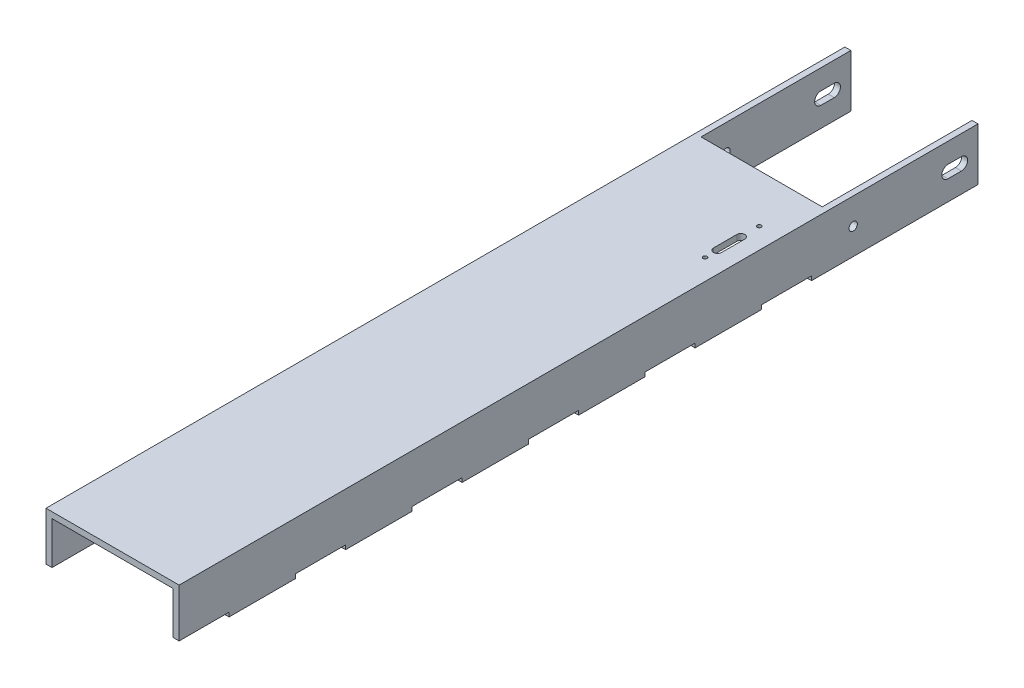
SolidWorks part; units mm, degrees
ref_plane "Front Plane" through (0, 0, 0) normal (0, 0, 1) x (1, 0, 0)
ref_plane "Top Plane" through (0, 0, 0) normal (0, 1, 0) x (1, 0, 0)
ref_plane "Right Plane" through (0, 0, 0) normal (1, 0, 0) x (0, 0, -1)
sketch "Sketch1" plane through (0, 0, 0) normal (0, 0, 1) x (1, 0, 0)
  line L0 (-50.8, 0) -> (50.8, 0)
  line L1 (50.8, 0) -> (50.8, -40.132)
  line L2 (50.8, -40.132) -> (46.228, -40.132)
  line L3 (46.228, -40.132) -> (46.228, -4.572)
  line L4 (46.228, -4.572) -> (-46.228, -4.572)
  line L5 (-46.228, -4.572) -> (-46.228, -40.132)
  line L6 (-46.228, -40.132) -> (-50.8, -40.132)
  line L7 (-50.8, -40.132) -> (-50.8, 0)
  point P8 (0, 0)
  dimension "D1" = 40.132
  dimension "D2" = 4.572
  dimension "D3" = 4.572
  dimension "D4" = 101.6
extrude "Boss-Extrude1" add sketch "Sketch1" along normal blind 609.6
sketch "Sketch3" plane through (0, 0, 0) normal (0, 1, 0) x (1, 0, 0)
  line L0 (50.8, 0) -> (-50.8, 0) construction
  line L1 (-46.228, -114.3) -> (46.228, -114.3)
  line L2 (-46.228, -114.3) -> (-46.228, 0)
  line L3 (-46.228, 0) -> (46.228, 0)
  line L4 (46.228, -114.3) -> (46.228, 0)
  line L5 (-46.228, -114.3) -> (46.228, 0) construction
  line L6 (-46.228, 0) -> (46.228, -114.3) construction
  line L7 (-46.228, -609.6) -> (-46.228, 0) construction
  line L8 (46.228, -609.6) -> (46.228, 0) construction
  line L9 (34.925, -165.1) -> (34.925, -182.88) construction
  line L10 (37.973, -165.1) -> (37.973, -182.88)
  line L11 (31.877, -165.1) -> (31.877, -182.88)
  arc A0 (37.973, -165.1) -> (31.877, -165.1) centre (34.925, -165.1) ccw
  arc A1 (31.877, -182.88) -> (37.973, -182.88) centre (34.925, -182.88) ccw
  circle A2 centre (34.925, -151.13) radius 1.524
  circle A3 centre (34.925, -192.405) radius 1.524
  point P0 (0, -57.15)
  point P13 (34.925, -173.99)
  dimension "D2" = 6.096
  dimension "D6" = 3.048
  dimension "D1" = 114.3
  dimension "D3" = 17.78
  dimension "D4" = 50.8
  dimension "D5" = 8.255
  dimension "D7" = 13.97
  dimension "D8" = 9.525
extrude "Cut-Extrude1" cut sketch "Sketch3" against normal through all
sketch "Sketch4" plane through (50.8, 0, 0) normal (1, 0, 0) x (0, 0, -1)
  line L0 (-12.7, -20.066) -> (-22.86, -20.066) construction
  line L1 (-12.7, -24.8285) -> (-22.86, -24.8285)
  line L2 (-12.7, -15.3035) -> (-22.86, -15.3035)
  line L3 (0, -40.132) -> (0, 0) construction
  line L4 (-520.7, -40.132) -> (-482.6, -40.132)
  line L5 (-609.6, -40.132) -> (-571.5, -40.132)
  line L6 (-609.6, -40.132) -> (-609.6, -36.957)
  line L7 (-609.6, -36.957) -> (-571.5, -36.957)
  line L8 (-571.5, -40.132) -> (-571.5, -36.957)
  line L9 (-520.7, -40.132) -> (-520.7, -36.957)
  line L10 (-520.7, -36.957) -> (-482.6, -36.957)
  line L11 (-482.6, -40.132) -> (-482.6, -36.957)
  line L12 (-431.8, -40.132) -> (-393.7, -40.132)
  line L13 (-431.8, -40.132) -> (-431.8, -36.957)
  line L14 (-431.8, -36.957) -> (-393.7, -36.957)
  line L15 (-393.7, -40.132) -> (-393.7, -36.957)
  line L16 (-342.9, -40.132) -> (-304.8, -40.132)
  line L17 (-342.9, -40.132) -> (-342.9, -36.957)
  line L18 (-342.9, -36.957) -> (-304.8, -36.957)
  line L19 (-304.8, -40.132) -> (-304.8, -36.957)
  line L20 (-254, -40.132) -> (-215.9, -40.132)
  line L21 (-254, -40.132) -> (-254, -36.957)
  line L22 (-254, -36.957) -> (-215.9, -36.957)
  line L23 (-215.9, -40.132) -> (-215.9, -36.957)
  line L24 (-165.1, -40.132) -> (-127, -40.132)
  line L25 (-165.1, -40.132) -> (-165.1, -36.957)
  line L26 (-165.1, -36.957) -> (-127, -36.957)
  line L27 (-127, -40.132) -> (-127, -36.957)
  arc A0 (-12.7, -24.8285) -> (-12.7, -15.3035) centre (-12.7, -20.066) ccw
  arc A1 (-22.86, -15.3035) -> (-22.86, -24.8285) centre (-22.86, -20.066) ccw
  circle A2 centre (-95.25, -20.066) radius 3.175
  point P3 (-17.78, -20.066)
  point P10 (0, -20.066)
  dimension "D3" = 9.525
  dimension "D5" = 6.35
  dimension "D1" = 10.16
  dimension "D2" = 12.7
  dimension "D4" = 95.25
  dimension "D6" = 3.175
  dimension "D7" = 38.1
  dimension "D8" = 6
extrude "Cut-Extrude2" cut sketch "Sketch4" against normal through all
